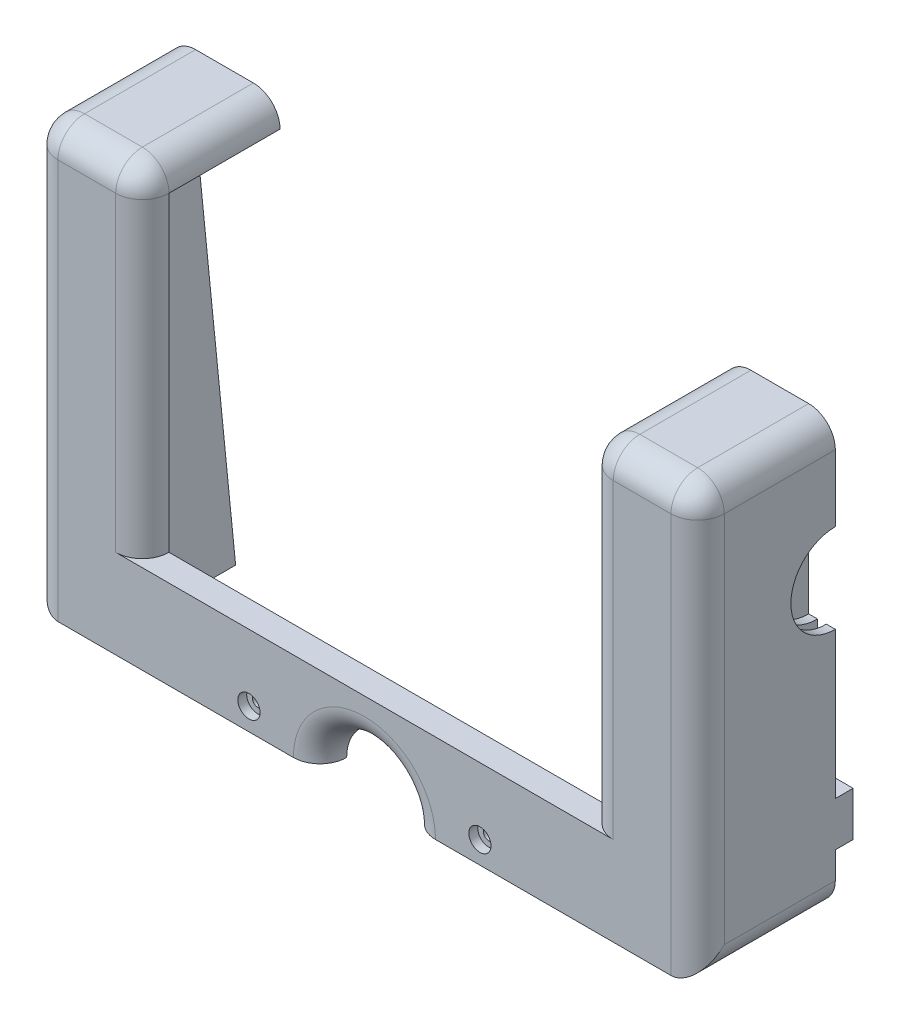
SolidWorks part; units mm, degrees
ref_plane "Front Plane" through (0, 0, 0) normal (0, 0, 1) x (1, 0, 0)
ref_plane "Top Plane" through (0, 0, 0) normal (0, 1, 0) x (1, 0, 0)
ref_plane "Right Plane" through (0, 0, 0) normal (1, 0, 0) x (0, 0, -1)
sketch "Sketch2" plane through (0, 0, 0) normal (0, 0, 1) x (1, 0, 0)
  line L1 (-37.5, 25.5) -> (37.5, 25.5)
  line L2 (-37.5, 25.5) -> (-37.5, -22.5)
  line L3 (-37.5, -22.5) -> (37.5, -22.5)
  line L4 (37.5, 25.5) -> (37.5, -22.5)
  dimension "D1" = 75
  dimension "D2" = 48
  dimension "D3" = 37.5
  dimension "D4" = 25.5
extrude "Boss-Extrude1" add sketch "Sketch2" along normal mid plane 15.5
sketch "Sketch11" plane through (0, 0, -7.75) normal (0, 0, -1) x (-1, 0, 0)
  line L0 (-35, 22.5) -> (35, 22.5)
  line L1 (-30, -22.5) -> (30, -22.5)
  line L2 (37.5, -22.5) -> (-37.5, -22.5) construction
  line L3 (-35, 22.5) -> (-30, -22.5)
  line L4 (35, 22.5) -> (30, -22.5)
  dimension "D1" = 70
  dimension "D2" = 60
  dimension "D3" = 45
  dimension "D4" = 2.5
  dimension "D5" = 7.5
extrude "Cut-Extrude4" cut sketch "Sketch11" against normal blind 12.5
sketch "Sketch12" plane through (0, 0, 0) normal (0, 0, 1) x (1, 0, 0)
  line L0 (37.5, 25.5) -> (-37.5, 25.5) construction
  line L1 (-25, 25.5) -> (25, 25.5)
  line L2 (-25, 25.5) -> (-25, -12.5)
  line L3 (-25, -12.5) -> (25, -12.5)
  line L4 (25, 25.5) -> (25, -12.5)
  dimension "D1" = 50
  dimension "D2" = 38
  dimension "D3" = 12.5
extrude "Cut-Extrude5" cut sketch "Sketch12" against normal mid plane 15.5
sketch "Sketch13" plane through (0, 0, 0) normal (0, 0, 1) x (1, 0, 0)
  line L0 (-37.5, -22.5) -> (37.5, -22.5) construction
  line L1 (0, 0) -> (0, -39.5579) construction
  line L2 (-5, -22.5) -> (5, -22.5)
  circle A0 centre (13, -20) radius 0.625
  circle A1 centre (-13, -20) radius 0.625
  arc A2 (5, -22.5) -> (-5, -22.5) centre (0, -22.5) ccw
  dimension "D1" = 1.25
  dimension "D2" = 2.5
  dimension "D3" = 13
  dimension "D4" = 10
extrude "Cut-Extrude6" cut sketch "Sketch13" along normal through all
fillet "Fillet4" radius 3 13 edges at (0, -17.5, 7.75) (37.5, 1.5, 7.75) (25, 6.5, 7.75) (-25, 6.5, 7.75) (-37.5, 1.5, 7.75) (25, 25.5, 0) (-25, 25.5, 0) (-37.5, 25.5, 0) (37.5, 25.5, 0) (31.25, 25.5, 7.75) (-31.25, 25.5, 7.75) (-37.5, -22.5, 0) (37.5, -22.5, 0)
sketch "Sketch14" plane through (0, 0, -7.75) normal (0, 0, -1) x (-1, 0, 0)
  line L0 (-37.5, -19.5) -> (-37.5, 22.5) construction
  line L5 (0, 0) -> (0, -29.7272) construction
  line L6 (-37.5, -11.5) -> (-35.5, -11.5)
  line L7 (-37.5, -11.5) -> (-37.5, -16.5)
  line L8 (-37.5, -16.5) -> (-35.5, -16.5)
  line L9 (-35.5, -11.5) -> (-35.5, -16.5)
  line L15 (37.5, -16.5) -> (35.5, -16.5)
  line L16 (35.5, -11.5) -> (35.5, -16.5)
  line L17 (37.5, -11.5) -> (35.5, -11.5)
  line L18 (37.5, -11.5) -> (37.5, -16.5)
  arc A0 (-37.5, -19.5) -> (-34.5, -22.5) centre (-34.5, -19.5) ccw construction
  dimension "D1" = 3
  dimension "D2" = 5
  dimension "D3" = 2
extrude "Boss-Extrude2" add sketch "Sketch14" along normal blind 2
sketch "Sketch16" plane through (0, 0, 7.75) normal (0, 0, 1) x (1, 0, 0)
  line L0 (0, 0) -> (0, -30.349) construction
  circle A0 centre (-13, -20) radius 1.25
  circle A2 centre (13, -20) radius 1.25
  dimension "D1" = 2.5
extrude "Cut-Extrude9" cut sketch "Sketch16" against normal blind 1
sketch "Sketch18" plane through (37.5, 0, 0) normal (1, 0, 0) x (0, 0, -1)
  line L0 (7.75, -11.5) -> (7.75, 22.5) construction
  circle A0 centre (7.75, 10) radius 5
  dimension "D1" = 10
  dimension "D2" = 10
extrude "Cut-Extrude10" cut sketch "Sketch18" against normal blind 3
ref_plane "Plane1" through (36, 0, 0) normal (1, 0, 0) x (0, 0, -1)
sketch "Sketch19" plane through (36, 0, 0) normal (1, 0, 0) x (0, 0, -1)
  line L0 (7.75, 5) -> (7.75, 15) construction
  circle A0 centre (7.75, 10) radius 7.5
  dimension "D1" = 15
extrude "Cut-Extrude11" cut sketch "Sketch19" against normal mid plane 1
mirror "Mirror1" about plane through (0, 0, 0) normal (1, 0, 0) of "Cut-Extrude11", "Cut-Extrude10"
